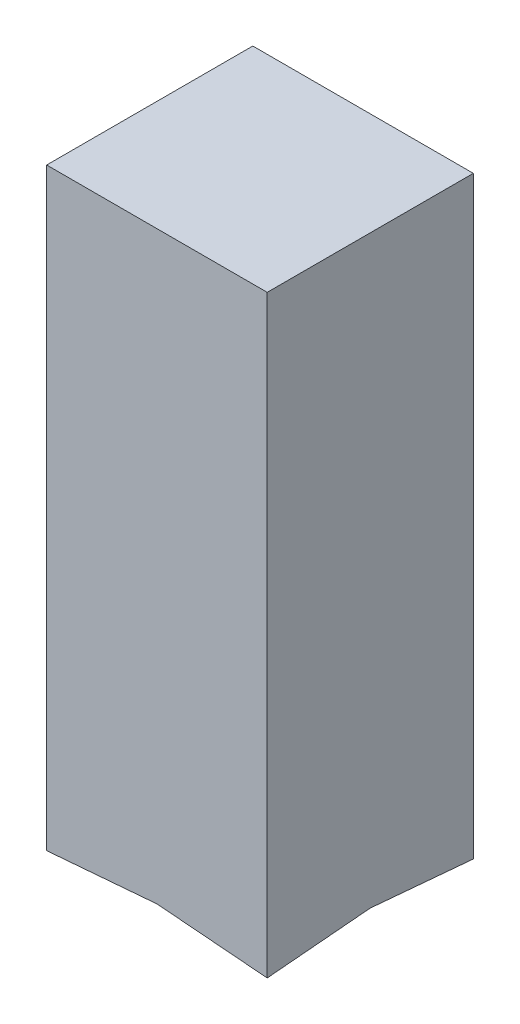
SolidWorks part; units mm, degrees
material "K110"
ref_plane "Front Plane" through (0, 0, 0) normal (0, 0, 1) x (1, 0, 0)
ref_plane "Top Plane" through (0, 0, 0) normal (0, 1, 0) x (1, 0, 0)
ref_plane "Right Plane" through (0, 0, 0) normal (1, 0, 0) x (0, 0, -1)
sketch "Sketch1" plane through (0, 0, 0) normal (0, 1, 0) x (1, 0, 0)
  line L1 (-10.25, -9.58) -> (10.25, -9.58)
  line L2 (-10.25, -9.58) -> (-10.25, 9.58)
  line L3 (-10.25, 9.58) -> (10.25, 9.58)
  line L4 (10.25, -9.58) -> (10.25, 9.58)
  line L5 (-10.25, -9.58) -> (10.25, 9.58) construction
  line L6 (-10.25, 9.58) -> (10.25, -9.58) construction
  point P0 (0, 0)
  dimension "D1" = 19.16
  dimension "D2" = 20.5
extrude "Boss-Extrude1" add sketch "Sketch1" against normal blind 55.2
sketch "Sketch5" plane through (10.25, 0, 0) normal (1, 0, 0) x (0, 0, -1)
  line L0 (-9.58, -55.2) -> (0, -54.3619)
  line L1 (0, -54.3619) -> (9.58, -55.2)
  line L2 (9.58, -55.2) -> (-9.58, -55.2)
  point P5 (0, 0)
  dimension "D1" = 5
extrude "Cut-Extrude3" cut sketch "Sketch5" against normal through all
sketch "Sketch6" plane through (0, 0, -9.58) normal (0, 0, -1) x (-1, 0, 0)
  line L0 (-10.25, -55.2) -> (0, -54.3619)
  line L1 (10.25, -54.3619) -> (-10.25, -54.3619) construction
  line L2 (0, -54.3619) -> (10.25, -55.2)
  line L3 (10.25, -55.2) -> (-10.25, -55.2)
  dimension "D1" = 4.675
extrude "Cut-Extrude4" cut sketch "Sketch6" against normal through all
